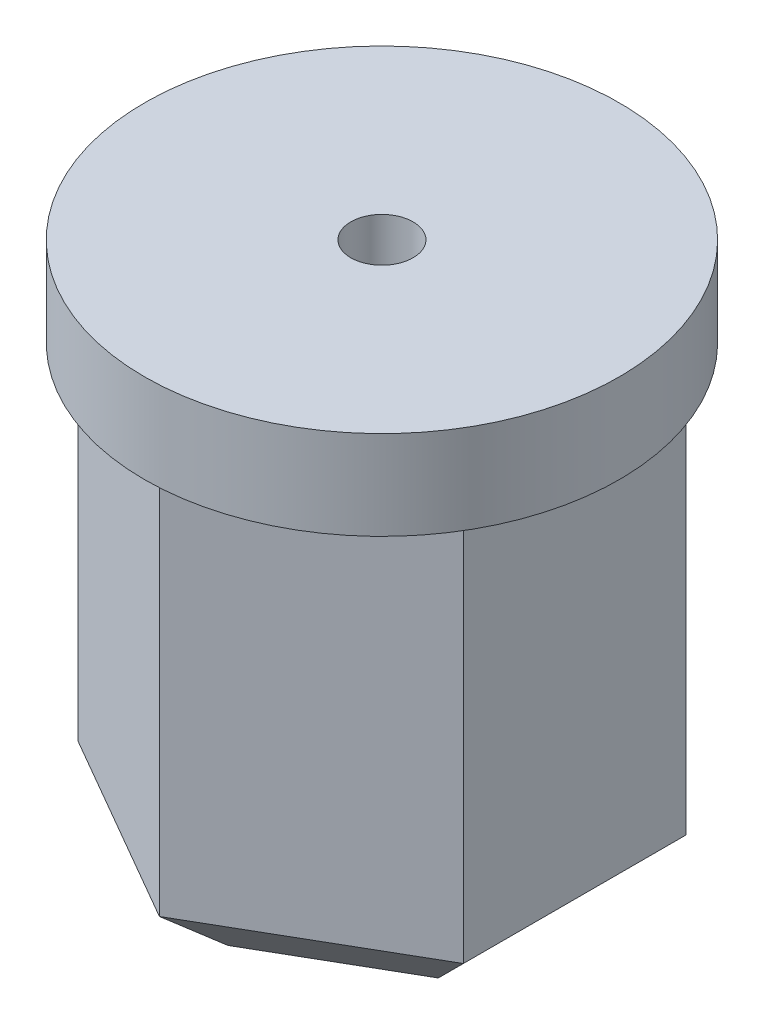
SolidWorks part; units mm, degrees
ref_plane "Front Plane" through (0, 0, 0) normal (0, 0, 1) x (1, 0, 0)
ref_plane "Top Plane" through (0, 0, 0) normal (0, 1, 0) x (1, 0, 0)
ref_plane "Right Plane" through (0, 0, 0) normal (1, 0, 0) x (0, 0, -1)
sketch "Sketch1" plane through (0, 0, 0) normal (0, 1, 0) x (1, 0, 0)
  circle A0 centre (0, 0) radius 8
  dimension "D1" = 16
extrude "Boss-Extrude1" add sketch "Sketch1" along normal blind 3
ref_axis "Axis1" through (0, 13.8986, 0) along (0, -1, 0)
sketch "Sketch9" plane through (0, 0, 0) normal (0, -1, 0) x (1, 0, 0)
  line L1 (0, -7.5) -> (6.4952, -3.75)
  line L2 (6.4952, -3.75) -> (6.4952, 3.75)
  line L3 (6.4952, 3.75) -> (0, 7.5)
  line L4 (0, 7.5) -> (-6.4952, 3.75)
  line L5 (-6.4952, 3.75) -> (-6.4952, -3.75)
  line L6 (-6.4952, -3.75) -> (0, -7.5)
  circle A0 centre (0, 0) radius 7.5
  circle A1 centre (0, 0) radius 6.4952 construction
  dimension "D1" = 15
extrude "Boss-Extrude2" add sketch "Sketch9" along normal blind 15 contours L1 L2 L3 L4 L5 L6
chamfer "Chamfer1" distance 2 angle 45 6 edges at (-6.4952, -15, 0) (-3.2476, -15, 5.625) (3.2476, -15, 5.625) (6.4952, -15, 0) (3.2476, -15, -5.625) (-3.2476, -15, -5.625)
sketch "Sketch10" plane through (0, -15, 0) normal (0, -1, 0) x (1, 0, 0)
  circle A0 centre (0, 0) radius 2.5
  dimension "D1" = 5
extrude "Cut-Extrude1" cut sketch "Sketch10" against normal up to surface (15 mm away) up to face at (0, 0, 8)
sketch "Sketch11" plane through (0, 3, 0) normal (0, 1, 0) x (1, 0, 0)
  circle A0 centre (0, 0) radius 1.984 construction
  circle A1 centre (0, 0) radius 1.984
  circle A2 centre (0, 0) radius 1.05
  dimension "D1" = 2.1
extrude "Cut-Extrude3" cut sketch "Sketch11" against normal through all contours A2 region at (0, 3, 0)
